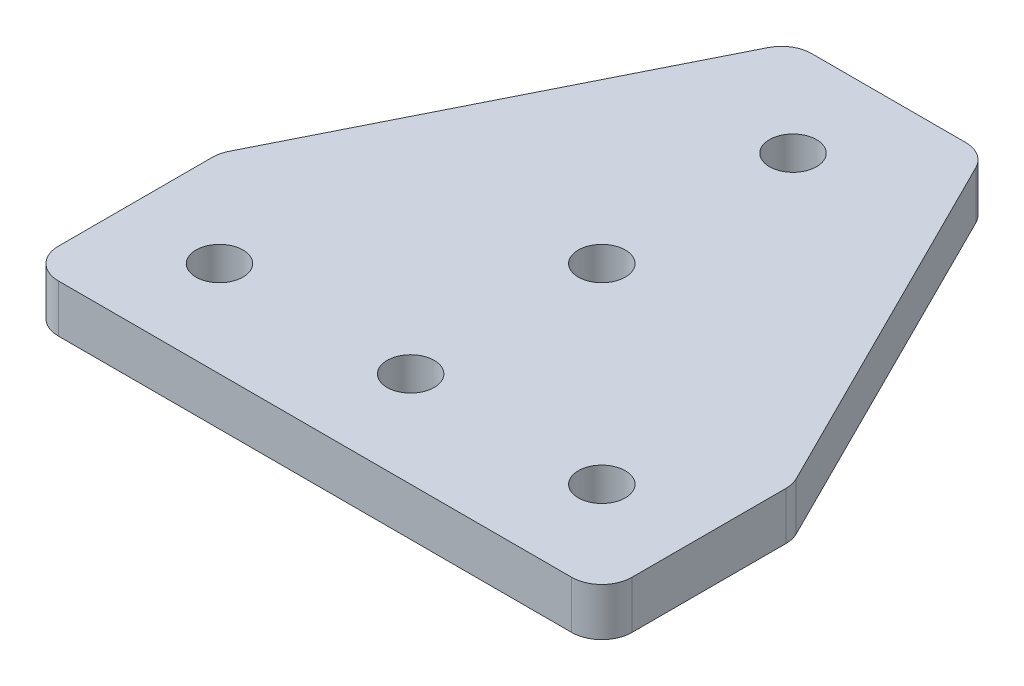
SolidWorks part; units mm, degrees
ref_plane "Front Plane" through (0, 0, 0) normal (0, 0, 1) x (1, 0, 0)
ref_plane "Top Plane" through (0, 0, 0) normal (0, 1, 0) x (1, 0, 0)
ref_plane "Right Plane" through (0, 0, 0) normal (1, 0, 0) x (0, 0, -1)
sketch "Sketch1" plane through (0, 0, 0) normal (0, 1, 0) x (1, 0, 0)
  line L0 (0, 0) -> (0, 25.4) construction
  line L1 (0, 25.4) -> (0, 50.8) construction
  line L2 (0, 0) -> (25.4, 0) construction
  line L3 (0, 0) -> (-25.4, 0) construction
  line L4 (0, -12.7) -> (-38.1, -12.7)
  line L5 (-38.1, -12.7) -> (-38.1, 12.7)
  line L6 (-38.1, 12.7) -> (-12.7, 63.5)
  line L7 (-12.7, 63.5) -> (12.7, 63.5)
  line L8 (12.7, 63.5) -> (38.1, 12.7)
  line L9 (38.1, 12.7) -> (38.1, -12.7)
  line L10 (38.1, -12.7) -> (0, -12.7)
  line L11 (0, 50.8) -> (0, 63.5) construction
  line L12 (0, -12.7) -> (0, 0) construction
  line L13 (-25.4, 0) -> (-38.1, 0) construction
  circle A0 centre (0, 50.8) radius 3.125
  circle A1 centre (0, 25.4) radius 3.125
  circle A2 centre (25.4, 0) radius 3.125
  circle A3 centre (0, 0) radius 3.125
  circle A4 centre (-25.4, 0) radius 3.125
  dimension "D2" = 6.25
  dimension "D1" = 25.4
  dimension "D3" = 25.4
  dimension "D4" = 76.2
  dimension "D5" = 25.4
  dimension "D6" = 38.1
extrude "Boss-Extrude1" add sketch "Sketch1" along normal blind 6.35
fillet "Fillet1" radius 4 6 edges at (12.7, 3.175, -63.5) (-12.7, 3.175, -63.5) (-38.1, 3.175, -12.7) (-38.1, 3.175, 12.7) (38.1, 3.175, 12.7) (38.1, 3.175, -12.7)
